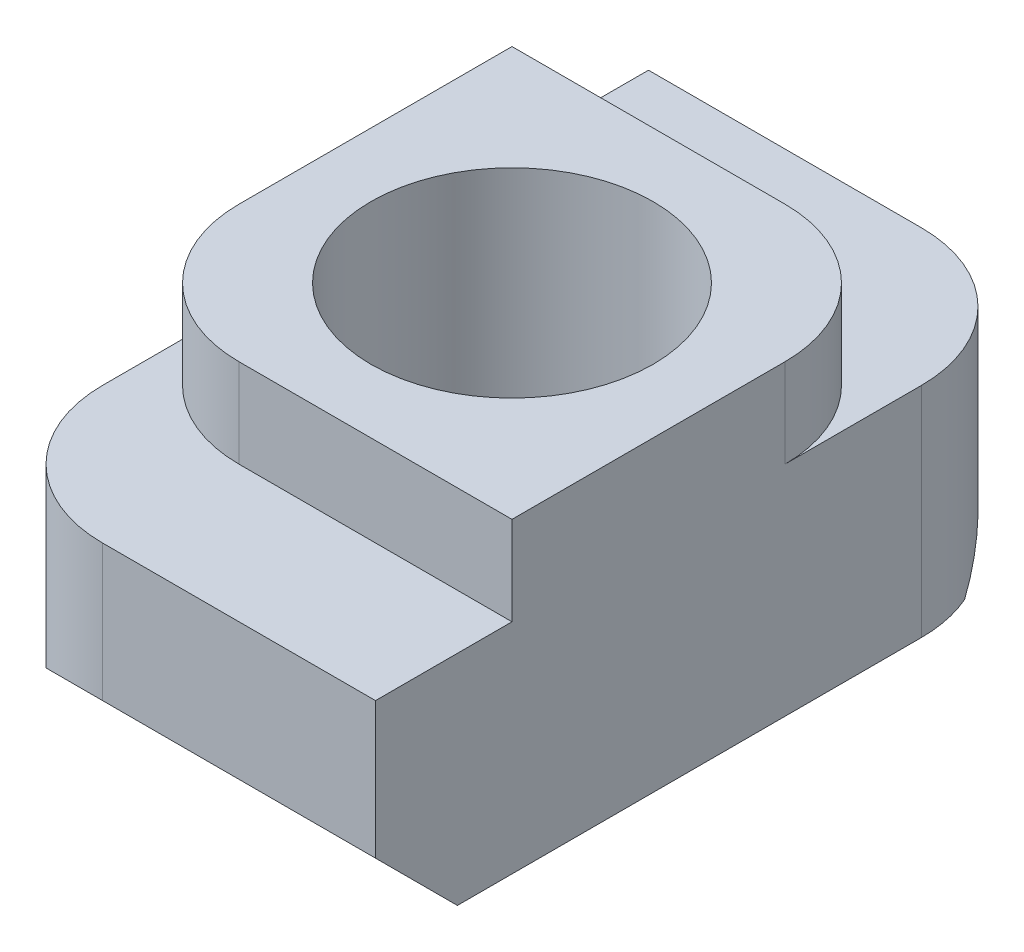
SolidWorks part; units mm, degrees
ref_plane "Front Plane" through (0, 0, 0) normal (0, 0, 1) x (1, 0, 0)
ref_plane "Top Plane" through (0, 0, 0) normal (0, 1, 0) x (1, 0, 0)
ref_plane "Right Plane" through (0, 0, 0) normal (1, 0, 0) x (0, 0, -1)
ref_axis "Axis_X" through (-88.99, 0, 0) along (1, 0, 0)
ref_axis "Axis_Y" through (0, 55, 0) along (0, -1, 0)
ref_axis "Axis_Z" through (0, 0, -88.99) along (0, 0, 1)
sketch "Sketch1" plane through (0, 0, 0) normal (1, 0, 0) x (0, 0, -1)
  line L0 (-3, 0) -> (3, 0)
  line L1 (3, 0) -> (3, -1.3)
  line L2 (3, -1.3) -> (5, -1.3)
  line L3 (5, -1.3) -> (5, -3.3)
  line L4 (5, -3.3) -> (3.8, -4.5)
  line L5 (3.8, -4.5) -> (-3.8, -4.5)
  line L6 (-3.8, -4.5) -> (-5, -3.3)
  line L7 (-5, -3.3) -> (-5, -1.3)
  line L8 (-5, -1.3) -> (-3, -1.3)
  line L9 (-3, -1.3) -> (-3, 0)
  line L10 (0, 0) -> (0, -4.5) construction
  dimension "FIX_1" = 45
  dimension "FIX_2" = 10
  dimension "FIX_3" = 6
  dimension "FIX_4" = 3.2
  dimension "FIX_5" = 2
  dimension "FIX_6" = 4.5
extrude "Boss-Extrude1" add sketch "Sketch1" along normal mid plane 6
fillet "Fillet1" radius 2 4 edges at (3, -2.3, -5) (-3, -2.3, 5) (3, -0.65, -3) (-3, -0.65, 3)
hole_wizard "Tap1" positions "Sketch3" profile "Sketch2" hole size "M3x0.5" standard "JIS" end condition through all
sketch "Sketch3" plane through (0, 0, 0) normal (0, 1, 0) x (1, 0, 0)
  point P0 (0, 0)
sketch "Sketch2" plane through (0, 0, 0) normal (1, 0, 0) x (0, 0, 1)
  line L0 (0, 0) -> (0, 4.5)
  line L1 (0, 4.5) -> (2.067, 4.5)
  line L2 (2.067, 4.5) -> (2.067, 0)
  line L5 (2.067, 0) -> (0, 0)
  line L11 (0, -6.35) -> (0, 107.95) construction
  dimension "FIX_9" = 4.134
  dimension "Thru Hole Depth" = 4.5
cosmetic thread "Thread1" parameters "FIX_10"=5
equation "\"Factor\"= 1.082532"
